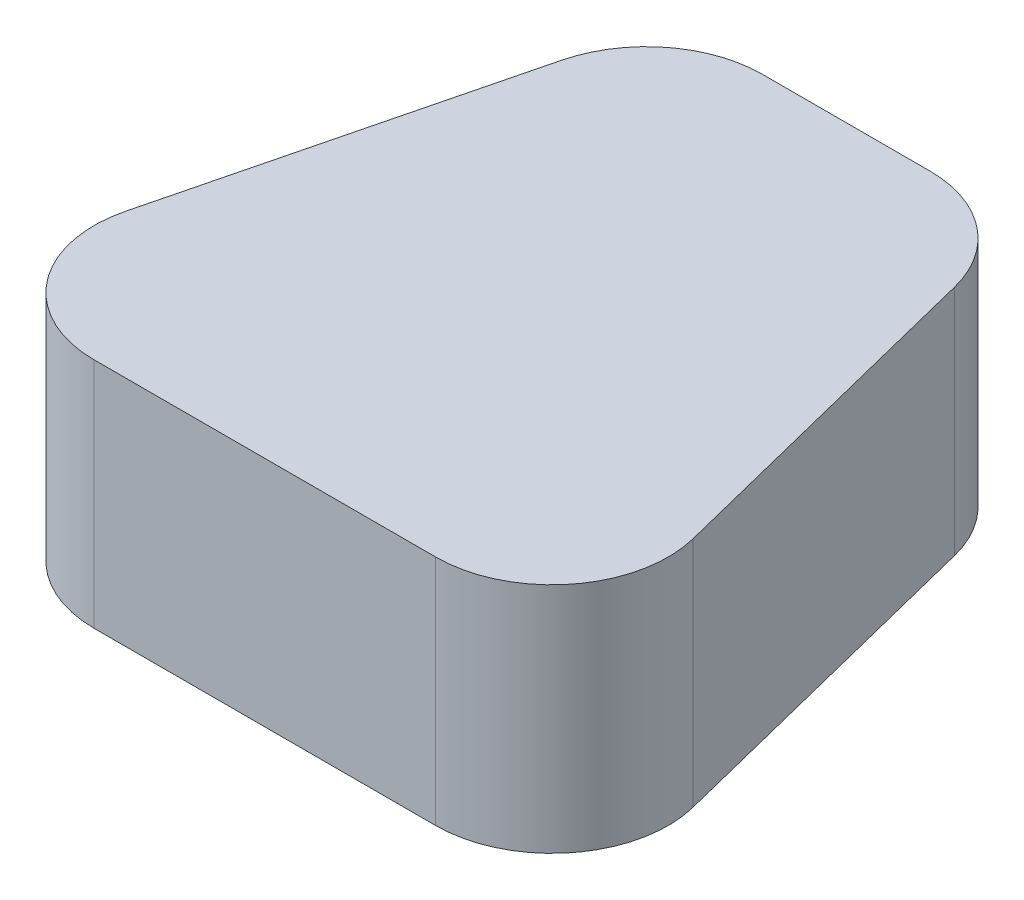
SolidWorks part; units mm, degrees
material "ABS"
ref_plane "前视基准面" through (0, 0, 0) normal (0, 0, 1) x (1, 0, 0)
ref_plane "上视基准面" through (0, 0, 0) normal (0, 1, 0) x (1, 0, 0)
ref_plane "右视基准面" through (0, 0, 0) normal (1, 0, 0) x (0, 0, -1)
ref_plane "ConnectFace" through (0, 0, 0) normal (0, 1, 0) x (1, 0, 0)
ref_plane "CenterV" through (0, 0, 0) normal (1, 0, 0) x (0, 0, -1)
ref_plane "CenterH" through (0, 0, 0) normal (0, 0, 1) x (1, 0, 0)
ref_axis "CenterAxis" through (0, -55, 0) along (0, 1, 0)
sketch "AssemSketch" plane through (0, 0, 0) normal (0, 1, 0) x (1, 0, 0)
  line L0 (0, 25) -> (0, -25) construction
  line L1 (-32.0863, 0) -> (32.0863, 0) construction
  line L2 (0, 0) -> (6.8416, -3.95) construction
  circle A0 centre (0, 0) radius 20
  dimension "H" = 50
  dimension "PinCircle" = 40
  dimension "ang" = 30
  dimension "F" = 7.9
ref_plane "WireConnectFace" through (0, 0, 25) normal (0, 0, 1) x (1, 0, 0)
ref_plane "HeadFace" through (0, 0, 0) normal (0, 1, 0) x (1, 0, 0)
ref_plane "PinCenterH" through (0, 0, 0) normal (-0.5, 0, 0.866) x (0.866, 0, 0.5)
ref_plane "PinCenterV" through (6.8416, 0, 3.95) normal (0.866, 0, 0.5) x (0.5, 0, -0.866)
sketch "SShape1" plane through (0, 0, 0) normal (0, 1, 0) x (1, 0, 0)
  line L0 (0, 25) -> (0, -25) construction
  line L1 (-15, 25) -> (15, 25)
  line L2 (15, 25) -> (27.5, -25)
  line L3 (27.5, -25) -> (-27.5, -25)
  line L4 (-27.5, -25) -> (-15, 25)
  line L5 (-21.25, 0) -> (21.25, 0) construction
  dimension "L1" = 30
  dimension "L2" = 55
  dimension "H" = 50
extrude "FShape1" add sketch "SShape1" along normal blind 20
fillet "FRShape1" radius 10 4 edges at (-15, 10, -25) (15, 10, -25) (27.5, 10, 25) (-27.5, 10, 25)
sketch "SShape2" [suppressed] plane through (0, 1, 0) normal (0, 1, 0) x (1, 0, 0)
  circle A0 centre (0, 0) radius 40
  dimension "D1" = 50
extrude "FShape2" [suppressed] add sketch "SShape2" along normal blind 20
equation "\"CtFaceTn\"= 1"
equation "\"H@SShape1\"=\"H@AssemSketch\""
equation "\"D1@SShape2\"=\"H@AssemSketch\""
equation "\"HeadH\"= 20"
equation "\"D1@FShape1\"=\"HeadH\""
equation "\"D1@FShape2\"=\"HeadH\""
